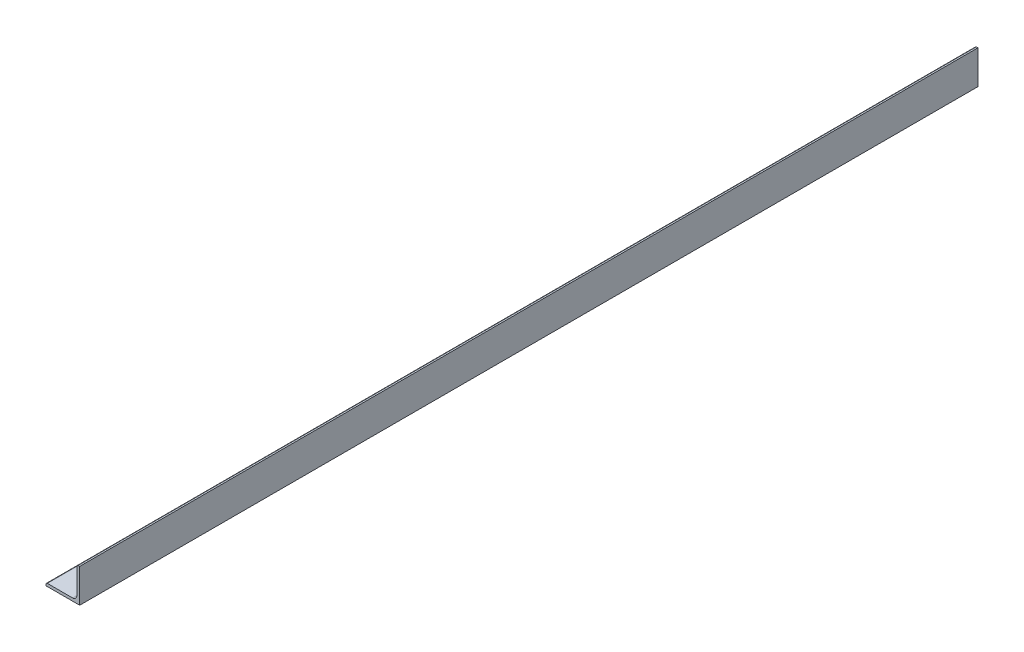
SolidWorks part; units mm, degrees
ref_plane "Front Plane" through (0, 0, 0) normal (0, 0, 1) x (1, 0, 0)
ref_plane "Top Plane" through (0, 0, 0) normal (0, 1, 0) x (1, 0, 0)
ref_plane "Right Plane" through (0, 0, 0) normal (1, 0, 0) x (0, 0, -1)
sketch "Sketch0" plane through (0, 0, 0) normal (0, 0, 1) x (1, 0, 0)
  line L0 (-9.525, -9.525) -> (9.525, -9.525)
  line L1 (9.525, -9.525) -> (9.525, 9.525)
  line L2 (9.525, 0) -> (0, 0) construction
  line L3 (0, 0) -> (0, -9.525) construction
  line L4 (7.9375, -5.5499) -> (7.9375, 9.525) construction
  line L5 (5.5499, -7.9375) -> (-9.525, -7.9375) construction
  arc A0 (7.9375, -5.5499) -> (5.5499, -7.9375) centre (5.5499, -5.5499) cw
  point P3 (7.2382, -7.2382)
  dimension "Inside Corner Radius" = 2.3876
  dimension "Outside Height" = 19.05
  dimension "Inside Height" = 17.4625
  dimension "Inside Width" = 17.4625
  dimension "Wall Thickness" = 1.5875
  dimension "D1" = 1.5875
  dimension "Outside Width" = 19.05
sketch "Sketch1" plane through (0, 0, 0) normal (1, 0, 0) x (0, 0, -1)
  line L0 (254, 0) -> (-254, 0)
  point P4 (0, 0)
  dimension "Length" = 508
sketch "Sketch2" plane through (0, 0, 0) normal (0, 0, 1) x (1, 0, 0)
  line L0 (-9.525, -9.525) -> (9.525, -9.525)
  line L1 (9.525, -9.525) -> (9.525, 9.525)
  line L2 (9.525, 9.525) -> (7.9375, 9.525) construction
  line L3 (7.9375, 8.7313) -> (7.9375, -5.5499)
  line L4 (5.5499, -7.9375) -> (-8.7313, -7.9375)
  line L5 (-9.525, -9.525) -> (-9.525, -7.9375) construction
  line L6 (8.7313, 9.525) -> (9.525, 9.525)
  line L7 (-9.525, -8.7313) -> (-9.525, -9.525)
  line L8 (9.525, 0) -> (0, 0) construction
  line L9 (0, 0) -> (0, -9.525) construction
  arc A0 (7.9375, 8.7313) -> (8.7313, 9.525) centre (8.7313, 8.7313) cw
  arc A1 (-9.525, -8.7313) -> (-8.7313, -7.9375) centre (-8.7313, -8.7313) cw
  arc A2 (7.9375, -5.5499) -> (5.5499, -7.9375) centre (5.5499, -5.5499) cw
  dimension "Inside Radius" = 2.3876
  dimension "Height" = 19.05
  dimension "Width" = 19.05
  dimension "Thickness" = 1.5875
extrude "Boss-Extrude1" add sketch "Sketch2" along normal mid plane 508
sketch "Break Locations" plane through (0, 0, 0) normal (1, 0, 0) x (0, 0, -1)
  line L0 (-234.569, 0) -> (234.569, 0)
  line L1 (-254, -9.525) -> (-254, 9.525) construction
  line L2 (254, -9.525) -> (254, 9.525) construction
  point P0 (-237.8075, 0)
  point P1 (237.8075, 0)
  point P10 (0, 0)
  point P11 (234.569, 0)
  point P13 (-234.569, 0)
  dimension "D1" = 16.1925
  dimension "D2" = 16.1925
  dimension "D3" = 19.431
hole_wizard "#10 Clearance Hole1" positions "Sketch3" profile "Sketch4" hole size "#10" standard "ANSI Inch"
sketch "Sketch3" plane through (0, -9.525, 0) normal (0, -1, 0) x (-1, 0, 0)
  point P2 (-3.175, 241.3)
  point P5 (-3.175, 215.9)
  point P8 (-3.175, -241.3)
  point P11 (-3.175, -215.9)
  point P14 (-3.1368, -241.3)
  point P16 (-3.1368, -215.9)
sketch "Sketch4" plane through (3.175, -9.525, -241.3) normal (1, 0, 0) x (0, 0, -1)
  line L0 (0, 0) -> (0, 4.7977)
  line L1 (0, 4.7977) -> (2.4892, 3.302)
  line L2 (2.4892, 3.302) -> (2.4892, 0)
  line L5 (2.4892, 0) -> (0, 0)
  line L10 (0, 4.7977) -> (-2.4892, 3.302) construction
  line L11 (0, -6.35) -> (0, 107.95) construction
  dimension "Hole Dia." = 4.9784
  dimension "Hole Depth" = 3.302
  dimension "Drill Angle" = 118
equation "\"D1@Break Locations\" = .85 * \"Height@Sketch2\""
equation "\"D2@Break Locations\"=\"D1@Break Locations\""
equation "\"Thickness@Sketch2\"=\"wall thickness@sketch0\""
equation "\"Height@Sketch2\"=\"outside height@sketch0\""
equation "\"Width@Sketch2\"=\"outside width@sketch0\""
equation "\"Inside Radius@Sketch2\"=\"inside corner radius@sketch0\""
equation "\"Length@Boss-Extrude1\"=\"length@sketch1\""
equation "\"D3@Break Locations\"=\"D2@Break Locations\"*1.2"
equation "\"D1@Sketch0\"=\"Wall Thickness@Sketch0\""
